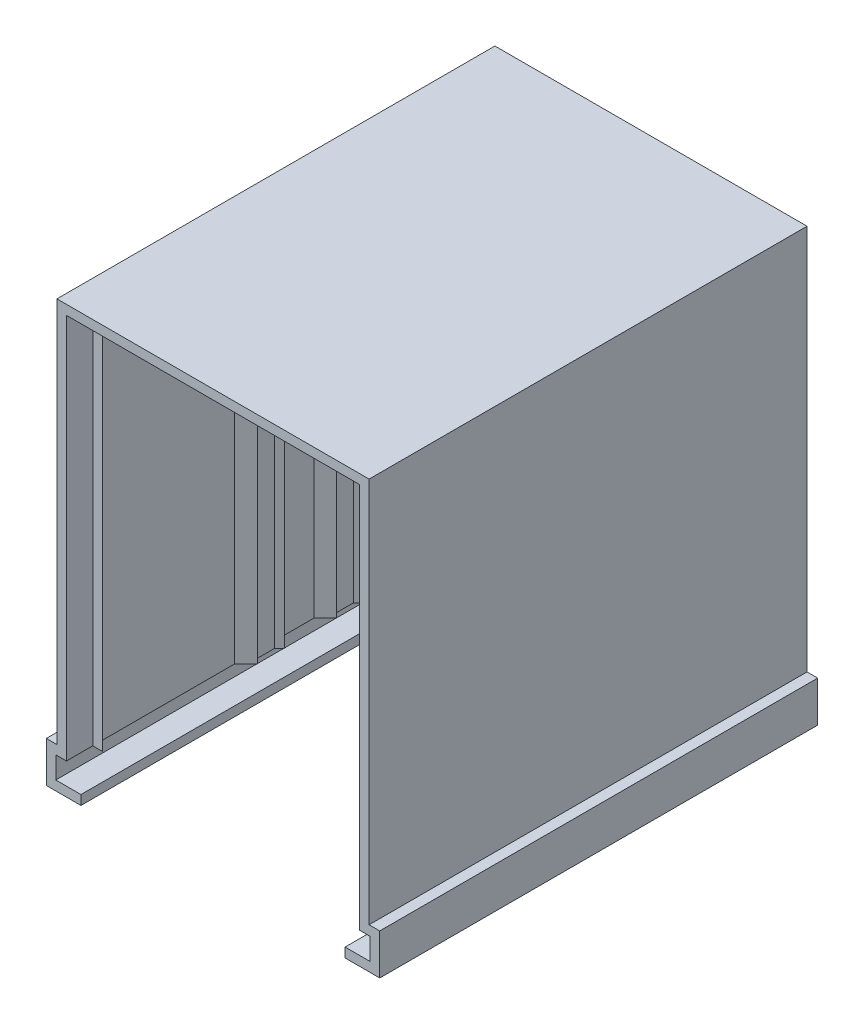
SolidWorks part; units mm, degrees
ref_plane "Front Plane" through (0, 0, 0) normal (0, 0, 1) x (1, 0, 0)
ref_plane "Top Plane" through (0, 0, 0) normal (0, 1, 0) x (1, 0, 0)
ref_plane "Right Plane" through (0, 0, 0) normal (1, 0, 0) x (0, 0, -1)
sketch "Sketch1" plane through (0, 0, 0) normal (0, 0, 1) x (1, 0, 0)
  line L0 (-14.81, 0.1) -> (-15.885, 0.1)
  line L1 (-15.885, 0.1) -> (-15.885, -2.1)
  line L7 (-14.81, 39.1) -> (-14.81, 0.1)
  line L8 (-14.71, 0) -> (-15.785, 0)
  line L9 (-15.785, 0) -> (-15.785, -2)
  line L10 (-15.785, -2) -> (15.785, -2)
  line L11 (15.785, -2) -> (15.785, 0)
  line L12 (15.785, 0) -> (14.71, 0)
  line L13 (14.71, 0) -> (14.71, 39)
  line L14 (14.71, 39) -> (-14.71, 39)
  line L15 (-14.71, 39) -> (-14.71, 0)
  line L16 (-14.71, 0) -> (-15.785, 0) construction
  line L17 (-15.785, 0) -> (-15.785, -2) construction
  line L18 (-15.785, -2) -> (15.785, -2) construction
  line L19 (15.785, -2) -> (15.785, 0) construction
  line L20 (15.785, 0) -> (14.71, 0) construction
  line L21 (14.71, 0) -> (14.71, 39) construction
  line L22 (14.71, 39) -> (-14.71, 39) construction
  line L23 (-14.71, 39) -> (-14.71, 0) construction
  line L24 (-15.885, -2.1) -> (15.885, -2.1) construction
  line L25 (-15.885, -2.1) -> (-13.345, -2.1)
  line L26 (-14.81, 39.1) -> (0, 39.1)
  line L27 (14.81, 0.1) -> (14.81, 39.1) construction
  line L28 (15.885, 0.1) -> (14.81, 0.1) construction
  line L29 (15.885, -2.1) -> (15.885, 0.1) construction
  line L30 (0, 43.8511) -> (0, -0.5601) construction
  line L31 (-15.77, 40.06) -> (0, 40.06)
  line L32 (14.81, 39.1) -> (-14.81, 39.1) construction
  line L33 (-15.77, 40.06) -> (-15.77, 1.06)
  line L34 (-15.77, 1.06) -> (-16.845, 1.06)
  line L35 (-16.845, 1.06) -> (-16.845, -3.06)
  line L36 (-16.845, -3.06) -> (-13.345, -3.06)
  line L37 (-13.345, -3.06) -> (-13.345, -2.1)
  line L38 (14.81, 39.1) -> (0, 39.1)
  line L39 (14.81, 39.1) -> (14.81, 0.1)
  line L40 (14.81, 0.1) -> (15.885, 0.1)
  line L41 (15.885, 0.1) -> (15.885, -2.1)
  line L42 (15.885, -2.1) -> (13.345, -2.1)
  line L43 (13.345, -3.06) -> (13.345, -2.1)
  line L44 (16.845, -3.06) -> (13.345, -3.06)
  line L45 (16.845, 1.06) -> (16.845, -3.06)
  line L46 (15.77, 1.06) -> (16.845, 1.06)
  line L47 (15.77, 40.06) -> (15.77, 1.06)
  line L48 (15.77, 40.06) -> (0, 40.06)
  dimension "D4" = 3.5
  dimension "D1" = 0
  dimension "D2" = 0.1
  dimension "D3" = 0.96
extrude "Boss-Extrude1" add sketch "Sketch1" against normal up to surface (44.25 mm away)
sketch "Sketch2" plane through (0, 39.1, 0) normal (0, -1, 0) x (1, 0, 0)
  line L0 (-14.81, -2.66) -> (-13.81, -2.66)
  line L1 (-14.81, -44.25) -> (-14.81, 0) construction
  line L2 (-13.81, -2.66) -> (-14.81, -3.66)
  line L3 (-14.81, -3.66) -> (-14.81, -2.66)
  line L4 (14.71, -2.56) -> (-14.71, -2.56) construction
  line L5 (0, 0) -> (0, -7.6274) construction
  line L6 (14.81, -3.66) -> (14.81, -2.66)
  line L7 (13.81, -2.66) -> (14.81, -3.66)
  line L8 (14.81, -2.66) -> (13.81, -2.66)
  dimension "D1" = 1
  dimension "D2" = 45
  dimension "D3" = 0.1
extrude "Boss-Extrude2" add sketch "Sketch2" along normal offset from surface (39 mm away) 0.1
sketch "Sketch3" plane through (0, 39.1, 0) normal (0, -1, 0) x (1, 0, 0)
  line L2 (-14.81, -44.25) -> (-14.81, -3.66) construction
  line L3 (-14.81, -32.99) -> (-14.81, -38.01)
  line L5 (-14.15, -36.35) -> (-14.15, -34.65)
  line L7 (-14.05, -34.75) -> (-14.05, -36.25) construction
  line L8 (-14.05, -34.75) -> (-14.05, -36.25) construction
  line L9 (-14.05, -35.5) -> (13.7849, -35.5) construction
  line L10 (0, 0) -> (0, -60.4865) construction
  line L11 (-14.15, -34.65) -> (-13.65, -34.15)
  line L12 (-13.65, -34.15) -> (-14.81, -32.99)
  line L13 (-13.65, -36.85) -> (-14.81, -38.01)
  line L14 (-14.15, -36.35) -> (-13.65, -36.85)
  line L15 (14.15, -36.35) -> (13.65, -36.85)
  line L16 (13.65, -36.85) -> (14.81, -38.01)
  line L17 (13.65, -34.15) -> (14.81, -32.99)
  line L18 (14.15, -34.65) -> (13.65, -34.15)
  line L19 (14.15, -36.35) -> (14.15, -34.65)
  line L20 (14.81, -32.99) -> (14.81, -38.01)
  point P6 (14.15, -35.5)
  point P7 (-14.81, -35.5)
  point P18 (-14.15, -35.5)
  point P19 (14.81, -35.5)
  dimension "D1" = 0.1
  dimension "D2" = 45
  dimension "D3" = 45
  dimension "D4" = 0.1
  dimension "D5" = 0.5
extrude "Boss-Extrude3" add sketch "Sketch3" along normal offset from surface (39 mm away) 0.1
pattern_linear "LPattern1" count 2 spacing 7 along (0, 0, -1) count 3 spacing 8 along (0, 0, 1) skipping (1, 1), (1, 2) of "Boss-Extrude3"
split "Split1" bodies to split 104 resulting bodies 105 106 107 split by face at (0, 10.0236, -44.25)
delete or keep bodies "Body-Delete/Keep 1" type delete bodies bodies 107 106
equation "\"offset\"=0.1"
equation "\"D1@Boss-Extrude2\"=\"offset\""
equation "\"D1@Sketch3\"=\"offset\""
equation "\"D4@Sketch3\"=\"offset\""
equation "\"D1@Boss-Extrude3\"=\"offset\""
